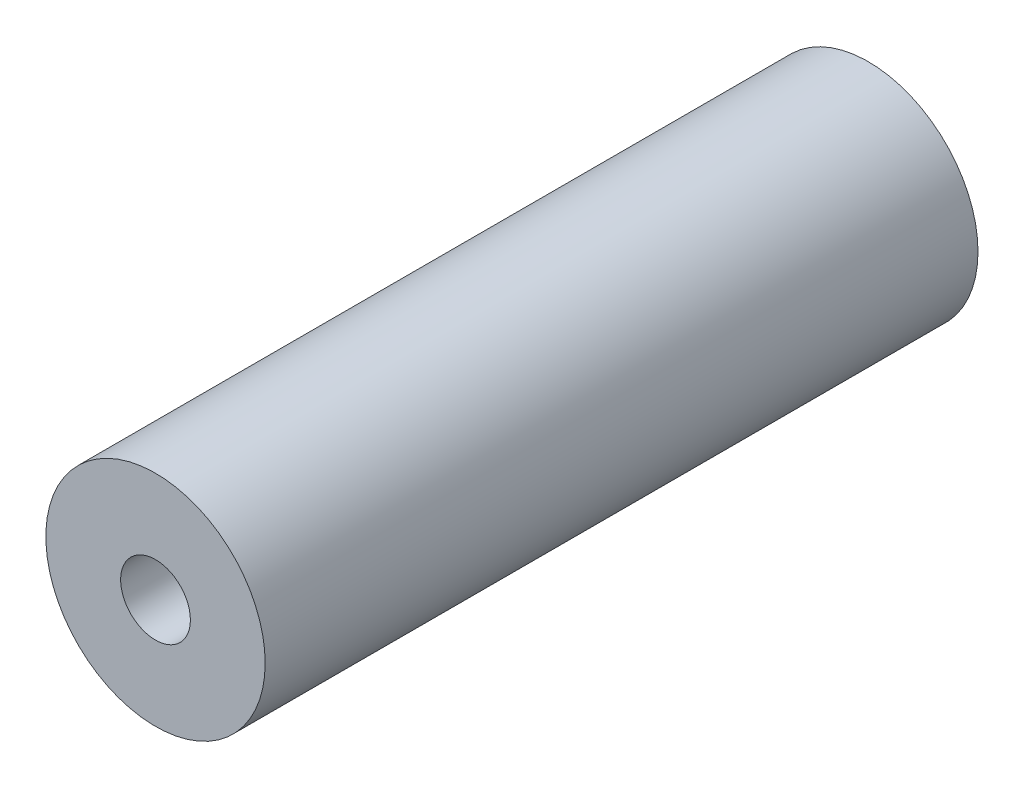
SolidWorks part; units mm, degrees
material "6061-T6 (SS)"
ref_plane "Front Plane" through (0, 0, 0) normal (0, 0, 1) x (1, 0, 0)
ref_plane "Top Plane" through (0, 0, 0) normal (0, 1, 0) x (1, 0, 0)
ref_plane "Right Plane" through (0, 0, 0) normal (1, 0, 0) x (0, 0, -1)
sketch "Sketch1" plane through (0, 0, 0) normal (0, 0, 1) x (1, 0, 0)
  circle A1 centre (0, 0) radius 6.35
  dimension "D2" = 12.7
extrude "Boss-Extrude1" add sketch "Sketch1" along normal mid plane 41.275 contours A1 region at (0, 0, 0)
hole_wizard "#10-32 Tapped Hole1" positions "3DSketch1" profile "Sketch2" tap size "#10-32" standard "ANSI Inch"
sketch3d "3DSketch1"
  line L0 (0, 0, 20.6375) -> (0, 0, -20.6375) construction
  point P0 (0, 0, 20.6375)
  point P4 (0, 0, -20.6375)
sketch "Sketch2" plane through (0, 0, 20.6375) normal (1, 0, 0) x (0, -1, 0)
  line L0 (0, 0) -> (0, 13.2428)
  line L1 (0, 13.2428) -> (2.0193, 12.0294)
  line L2 (2.0193, 12.0294) -> (2.0193, 0)
  line L5 (2.0193, 0) -> (0, 0)
  line L10 (0, 13.2428) -> (-2.0193, 12.0294) construction
  line L11 (0, -6.35) -> (0, 107.95) construction
  dimension "Tap Drill Dia." = 4.0386
  dimension "Tap Drill Depth" = 12.0294
  dimension "Drill Angle" = 118
cosmetic thread "Hole Thread1"
cosmetic thread "Hole Thread2"
